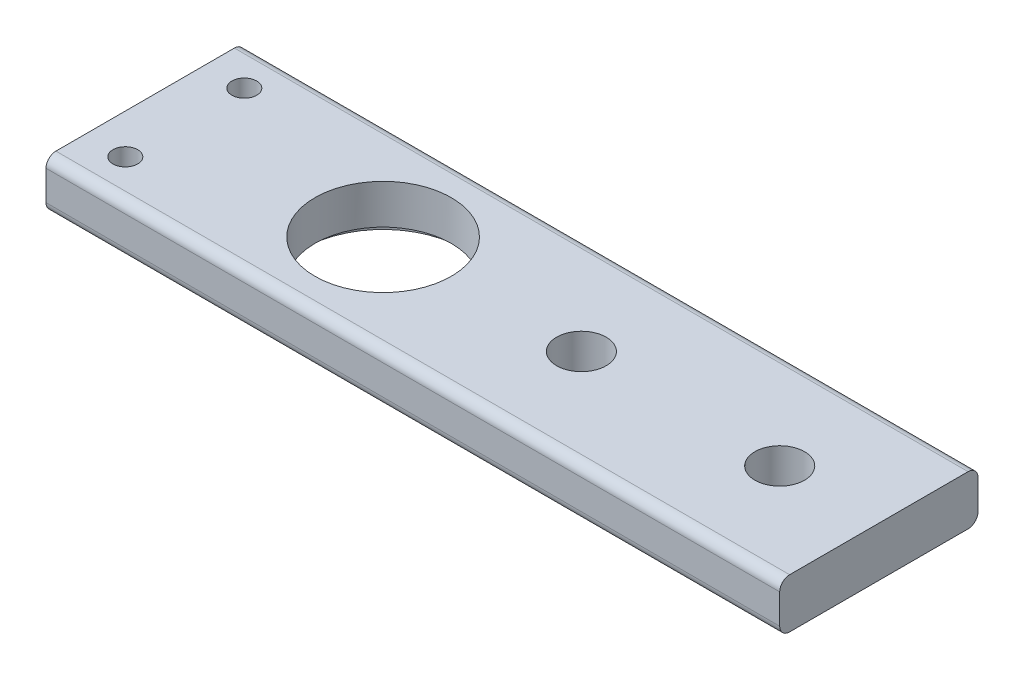
SolidWorks part; units mm, degrees
material "Plain Carbon Steel"
ref_plane "Front Plane" through (0, 0, 0) normal (0, 0, 1) x (1, 0, 0)
ref_plane "Top Plane" through (0, 0, 0) normal (0, 1, 0) x (1, 0, 0)
ref_plane "Right Plane" through (0, 0, 0) normal (1, 0, 0) x (0, 0, -1)
sketch "Sketch1" plane through (0, 0, 0) normal (0, 1, 0) x (1, 0, 0)
  line L1 (46.99, -12.7) -> (-46.99, -12.7)
  line L2 (46.99, -12.7) -> (46.99, 12.7)
  line L3 (46.99, 12.7) -> (-46.99, 12.7)
  line L4 (-46.99, -12.7) -> (-46.99, 12.7)
  line L5 (46.99, -12.7) -> (-46.99, 12.7) construction
  line L6 (46.99, 12.7) -> (-46.99, -12.7) construction
  point P0 (0, 0)
  dimension "D1" = 25.4
  dimension "D2" = 93.98
extrude "Boss-Extrude1" add sketch "Sketch1" along normal blind 6.35
fillet "Fillet1" radius 1.27 4 edges at (0, 0, -12.7) (0, 6.35, -12.7) (0, 0, 12.7) (0, 6.35, 12.7)
sketch "Sketch2" plane through (0, 6.35, 0) normal (0, 1, 0) x (1, 0, 0)
  line L0 (-46.99, 0) -> (46.99, 0) construction
  line L1 (-46.99, 11.43) -> (-46.99, -11.43) construction
  line L2 (46.99, -11.43) -> (46.99, 11.43) construction
  line L4 (8.89, 3.175) -> (34.29, 3.175) construction
  line L5 (8.89, 3.175) -> (8.89, -3.175) construction
  line L6 (8.89, -3.175) -> (34.29, -3.175) construction
  line L7 (34.29, 3.175) -> (34.29, -3.175) construction
  circle A0 centre (-41.91, 0) radius 1.5875 construction
  circle A1 centre (8.89, 0) radius 3.175
  circle A2 centre (34.29, 0) radius 3.175
  arc A4 (8.89, 3.175) -> (8.89, -3.175) centre (8.89, 0) ccw construction
  arc A5 (34.29, -3.175) -> (34.29, 3.175) centre (34.29, 0) ccw construction
  circle A6 centre (-16.51, 0) radius 8.7313
  circle A7 centre (-41.91, 7.62) radius 1.5875
  circle A8 centre (-41.91, -7.62) radius 1.5875
  dimension "D1" = 3.175
  dimension "D4" = 3.175
  dimension "D8" = 17.4625
  dimension "D3" = 5.08
  dimension "D5" = 25.4
  dimension "D6" = 25.4
  dimension "D7" = 25.4
  dimension "D9" = 7.62
  dimension "D10" = 7.62
extrude "Cut-Extrude1" cut sketch "Sketch2" against normal through all
sketch "Sketch3" plane through (0, 0, 0) normal (0, -1, 0) x (-1, 0, 0)
  circle A0 centre (16.51, 0) radius 10.16
  circle A1 centre (16.51, 0) radius 8.7313 construction
  dimension "D1" = 20.32
extrude "Cut-Extrude2" cut sketch "Sketch3" against normal blind 1.27
